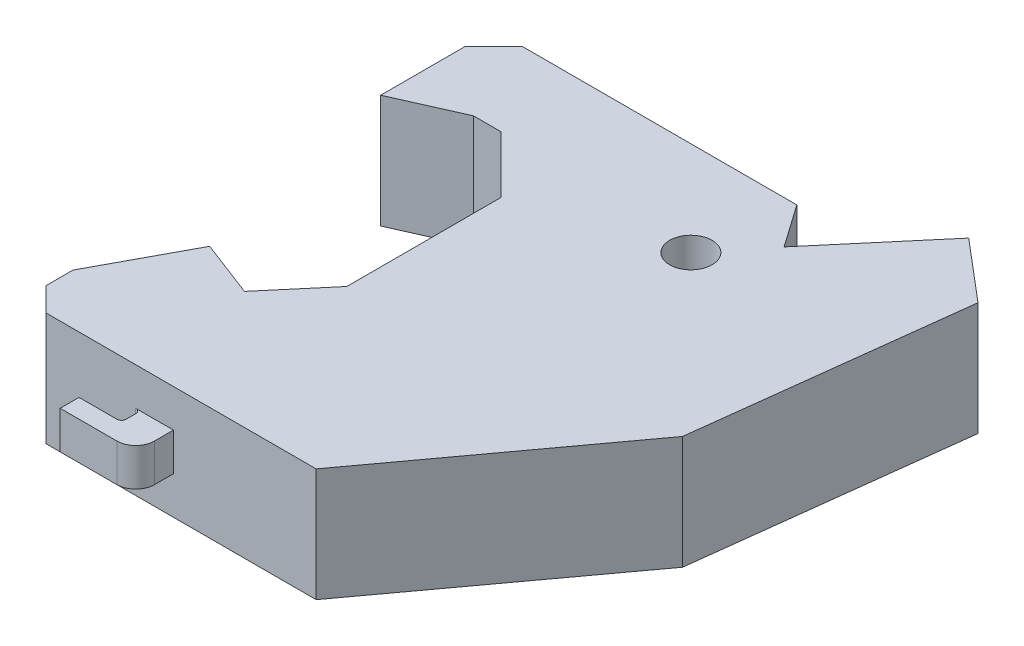
SolidWorks part; units mm, degrees
ref_plane "Front Plane" through (0, 0, 0) normal (0, 0, 1) x (1, 0, 0)
ref_plane "Top Plane" through (0, 0, 0) normal (0, 1, 0) x (1, 0, 0)
ref_plane "Right Plane" through (0, 0, 0) normal (1, 0, 0) x (0, 0, -1)
sketch "Sketch1" plane through (0, 0, 0) normal (0, 1, 0) x (1, 0, 0)
  line L0 (50.7574, 18.4002) -> (52.7574, 18.3985) construction
  line L18 (29.1219, 39.6749) -> (33.1219, 39.6749) construction
  line L19 (0, 0) -> (0, 5.3631)
  line L20 (0, 5.3631) -> (5.0593, 14.7799)
  line L21 (5.0593, 14.7799) -> (11.0365, 12.4849)
  line L22 (11.0365, 12.4849) -> (16.0077, 18.3562)
  line L23 (16.0077, 18.3562) -> (16.0077, 34.6664)
  line L24 (16.0077, 34.6664) -> (9.9532, 40.7209)
  line L25 (9.9532, 40.7209) -> (7.0643, 40.7209)
  line L26 (7.0643, 40.7209) -> (0.2549, 37.6936)
  line L27 (0.2549, 37.6936) -> (0.2549, 46.669)
  line L28 (0.2549, 46.669) -> (3.2584, 49.6724)
  line L29 (3.2584, 49.6724) -> (32.3615, 49.6724)
  line L30 (32.3615, 49.6724) -> (35.5373, 45.1461)
  line L31 (35.5373, 45.1461) -> (44.5039, 55.7364)
  line L32 (44.5039, 55.7364) -> (50.9267, 50.2983)
  line L33 (50.9267, 50.2983) -> (47.5466, 22.3821)
  line L34 (47.5466, 22.3821) -> (31.1166, 0)
  line L35 (31.1166, 0) -> (0, 0)
  circle A1 centre (31.1166, 39.6921) radius 2.25
  point P6 (0, 0)
  point P7 (0, 0)
  dimension "D2" = 4.5
  dimension "D1" = 4
extrude "Boss-Extrude1" add sketch "Sketch1" along normal blind 12
sketch "Sketch2" plane through (0, 0, 0) normal (0, 0, 1) x (1, 0, 0)
  line L0 (12, 0) -> (12, 12) construction
  line L1 (0, 0) -> (31.1166, 0) construction
  line L2 (0, 12) -> (31.1166, 12) construction
  line L4 (16, 8) -> (8, 8)
  line L5 (16, 8) -> (16, 4)
  line L6 (16, 4) -> (8, 4)
  line L7 (8, 8) -> (8, 4)
  line L8 (16, 8) -> (8, 4) construction
  line L9 (16, 4) -> (8, 8) construction
  point P6 (12, 6)
  dimension "D1" = 12
  dimension "D2" = 4
  dimension "D3" = 8
extrude "Boss-Extrude2" add sketch "Sketch2" along normal blind 4 contours L5 L4 L7 L6
sketch "Sketch3" plane through (0, 8, 0) normal (0, 1, 0) x (1, 0, 0)
  line L0 (12.5, -4) -> (12.5, 0) construction
  line L1 (16, -4) -> (8, -4) construction
  line L2 (0, 0) -> (31.1166, 0) construction
  line L4 (8, 0) -> (12, 0)
  line L5 (8, 0) -> (8, -2)
  line L6 (8, -2) -> (12, -2)
  line L7 (12.5, -0.5) -> (12.5, -1.5)
  line L9 (8, -4) -> (8, 0) construction
  line L14 (14, -4) -> (16, -4)
  line L15 (16, -4) -> (16, -2)
  arc A0 (12, -2) -> (12.5, -1.5) centre (12, -1.5) ccw
  arc A1 (12, 0) -> (12.5, -0.5) centre (12, -0.5) cw
  arc A2 (16, -2) -> (14, -4) centre (14, -2) cw
  point P13 (12.5, -2)
  point P30 (16, -4)
  dimension "D2" = 0.5
  dimension "D3" = 0.5
  dimension "D4" = 2
  dimension "D1" = 2
  dimension "D5" = 4
extrude "Cut-Extrude1" cut sketch "Sketch3" against normal blind 6
sketch "Sketch4" plane through (0, 12, 0) normal (0, 1, 0) x (1, 0, 0)
  line L0 (0, 0) -> (0, 2.5)
  line L1 (0, 5.3631) -> (0, 0) construction
  line L2 (0, 2.5) -> (2.5, 0)
  line L3 (0, 0) -> (31.1166, 0) construction
  line L4 (2.5, 0) -> (0, 0)
  dimension "D1" = 2.5
extrude "Cut-Extrude2" cut sketch "Sketch4" against normal through all contours L4 L0 L2
